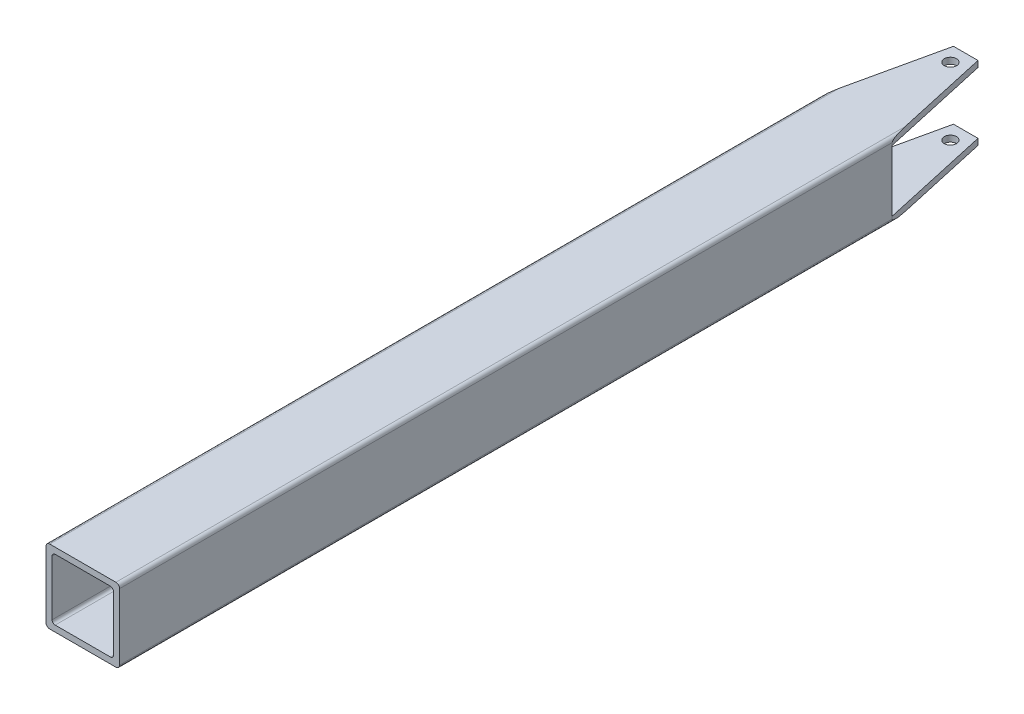
SolidWorks part; units mm, degrees
ref_plane "Front" through (0, 0, 0) normal (0, 0, 1) x (1, 0, 0)
ref_plane "Top" through (0, 0, 0) normal (0, 1, 0) x (1, 0, 0)
ref_plane "Right" through (0, 0, 0) normal (1, 0, 0) x (0, 0, -1)
sketch "Sketch1" plane through (0, 0, 0) normal (0, 0, 1) x (1, 0, 0)
  line L0 (-31.75, 0) -> (-38.1, 0) construction
  line L1 (34.29, -38.1) -> (-34.29, -38.1)
  line L2 (38.1, -34.29) -> (38.1, 34.29)
  line L3 (34.29, 38.1) -> (-34.29, 38.1)
  line L4 (-38.1, -34.29) -> (-38.1, 34.29)
  line L5 (38.1, -38.1) -> (-38.1, 38.1) construction
  line L6 (38.1, 38.1) -> (-38.1, -38.1) construction
  line L7 (28.575, 31.75) -> (-28.575, 31.75)
  line L8 (31.75, 28.575) -> (31.75, -28.575)
  line L9 (28.575, -31.75) -> (-28.575, -31.75)
  line L10 (-31.75, 28.575) -> (-31.75, -28.575)
  line L11 (31.75, 31.75) -> (-31.75, -31.75) construction
  line L12 (31.75, -31.75) -> (-31.75, 31.75) construction
  line L13 (0, -31.75) -> (0, -38.1) construction
  line L14 (31.75, -28.575) -> (31.75, -38.1) construction
  line L16 (31.75, -38.1) -> (38.1, -38.1) construction
  arc A0 (-28.575, -31.75) -> (-31.75, -28.575) centre (-28.575, -28.575) cw
  arc A1 (31.75, -28.575) -> (28.575, -31.75) centre (28.575, -28.575) cw
  arc A2 (28.575, 31.75) -> (31.75, 28.575) centre (28.575, 28.575) cw
  arc A3 (-28.575, 31.75) -> (-31.75, 28.575) centre (-28.575, 28.575) ccw
  arc A4 (34.29, -38.1) -> (38.1, -34.29) centre (34.29, -34.29) ccw
  arc A5 (38.1, 34.29) -> (34.29, 38.1) centre (34.29, 34.29) ccw
  arc A6 (-34.29, 38.1) -> (-38.1, 34.29) centre (-34.29, 34.29) ccw
  arc A7 (-34.29, -38.1) -> (-38.1, -34.29) centre (-34.29, -34.29) cw
  point P0 (0, 0)
  point P6 (0, 0)
  dimension "D2" = 3.175
  dimension "D3" = 3.81
sketch "Sketch2" plane through (0, 0, 0) normal (1, 0, 0) x (0, 0, -1)
  line L0 (-457.2, 0) -> (457.2, 0) construction
  dimension "Length" = 914.4
ref_plane "Plane1" through (38.1, 0, 0) normal (1, 0, 0) x (0, 0, -1)
sketch "Sketch5" plane through (38.1, 0, 0) normal (1, 0, 0) x (0, 0, -1)
  line L0 (-457.2, 38.1) -> (-457.2, -38.1) construction
  line L1 (457.2, 38.1) -> (457.2, -38.1) construction
sketch "Sketch4" plane through (0, 0, 0) normal (0, 0, 1) x (1, 0, 0)
  line L0 (38.1, -34.29) -> (38.1, 34.29) construction
  line L1 (34.29, 38.1) -> (-34.29, 38.1) construction
  line L2 (-38.1, -34.29) -> (-38.1, 34.29) construction
  line L3 (34.29, -38.1) -> (-34.29, -38.1) construction
  line L4 (31.75, 28.575) -> (31.75, -28.575) construction
  line L5 (28.575, -31.75) -> (-28.575, -31.75) construction
  line L6 (-31.75, 28.575) -> (-31.75, -28.575) construction
  line L7 (28.575, 31.75) -> (-28.575, 31.75) construction
  line L8 (38.1, -34.29) -> (38.1, 34.29)
  line L9 (34.29, 38.1) -> (-34.29, 38.1)
  line L10 (-38.1, -34.29) -> (-38.1, 34.29)
  line L11 (34.29, -38.1) -> (-34.29, -38.1)
  line L12 (31.75, 28.575) -> (31.75, -28.575)
  line L13 (28.575, -31.75) -> (-28.575, -31.75)
  line L14 (-31.75, 28.575) -> (-31.75, -28.575)
  line L15 (28.575, 31.75) -> (-28.575, 31.75)
  arc A0 (38.1, 34.29) -> (34.29, 38.1) centre (34.29, 34.29) ccw construction
  arc A1 (-34.29, 38.1) -> (-38.1, 34.29) centre (-34.29, 34.29) ccw construction
  arc A2 (-38.1, -34.29) -> (-34.29, -38.1) centre (-34.29, -34.29) ccw construction
  arc A3 (34.29, -38.1) -> (38.1, -34.29) centre (34.29, -34.29) ccw construction
  arc A4 (28.575, -31.75) -> (31.75, -28.575) centre (28.575, -28.575) ccw construction
  arc A5 (-31.75, -28.575) -> (-28.575, -31.75) centre (-28.575, -28.575) ccw construction
  arc A6 (-28.575, 31.75) -> (-31.75, 28.575) centre (-28.575, 28.575) ccw construction
  arc A7 (31.75, 28.575) -> (28.575, 31.75) centre (28.575, 28.575) ccw construction
  arc A8 (38.1, 34.29) -> (34.29, 38.1) centre (34.29, 34.29) ccw
  arc A9 (-34.29, 38.1) -> (-38.1, 34.29) centre (-34.29, 34.29) ccw
  arc A10 (-38.1, -34.29) -> (-34.29, -38.1) centre (-34.29, -34.29) ccw
  arc A11 (34.29, -38.1) -> (38.1, -34.29) centre (34.29, -34.29) ccw
  arc A12 (28.575, -31.75) -> (31.75, -28.575) centre (28.575, -28.575) ccw
  arc A13 (-31.75, -28.575) -> (-28.575, -31.75) centre (-28.575, -28.575) ccw
  arc A14 (-28.575, 31.75) -> (-31.75, 28.575) centre (-28.575, 28.575) ccw
  arc A15 (31.75, 28.575) -> (28.575, 31.75) centre (28.575, 28.575) ccw
extrude "Boss-Extrude1" add sketch "Sketch4" along normal up to vertex (457.2 mm away) and the other way up to vertex (457.2 mm away) up to point (0, 0, 457.2) other way up to point (0, 0, -457.2)
sketch "Sketch6" plane through (-38.1, 0, 0) normal (-1, 0, 0) x (0, 0, 1)
  line L0 (-457.2, -31.75) -> (-371.4675, -31.75) construction
  line L1 (-457.2, 31.75) -> (-342.9, 31.75)
  line L2 (-457.2, 31.75) -> (-457.2, -31.75)
  line L3 (-457.2, -31.75) -> (-342.9, -31.75)
  line L4 (-342.9, 31.75) -> (-342.9, -31.75)
  point P5 (-457.2, -31.75)
  dimension "D1" = 114.3
extrude "side cut" cut sketch "Sketch6" against normal through all
sketch "Sketch7" plane through (0, -38.1, 0) normal (0, -1, 0) x (1, 0, 0)
  line L0 (0, -457.2) -> (0, -341.7828) construction
  line L1 (-34.29, -457.2) -> (34.29, -457.2) construction
  line L2 (-38.1, -342.9) -> (-38.1, -457.2)
  line L3 (-38.1, -457.2) -> (-12.7, -457.2)
  line L4 (-12.7, -457.2) -> (-38.1, -342.9)
  line L5 (12.7, -457.2) -> (38.1, -342.9)
  line L6 (38.1, -457.2) -> (12.7, -457.2)
  line L7 (38.1, -342.9) -> (38.1, -457.2)
  dimension "D1" = 25.4
extrude "triangle cut" cut sketch "Sketch7" against normal through all
sketch "Sketch8" plane through (0, 38.1, 0) normal (0, 1, 0) x (1, 0, 0)
  line L0 (0, 457.2) -> (0, 353.4841) construction
  line L1 (12.7, 457.2) -> (-12.7, 457.2) construction
  circle A0 centre (0, 441.325) radius 6.35
  dimension "D1" = 12.7
  dimension "D2" = 15.875
extrude "Cut-Extrude4" cut sketch "Sketch8" against normal through all
equation "\"D3@Sketch1\"=\"Outside Width@Sketch1\"*.05"
equation "\"D2@Sketch1\"=\"D1@Sketch1\"*.05"
